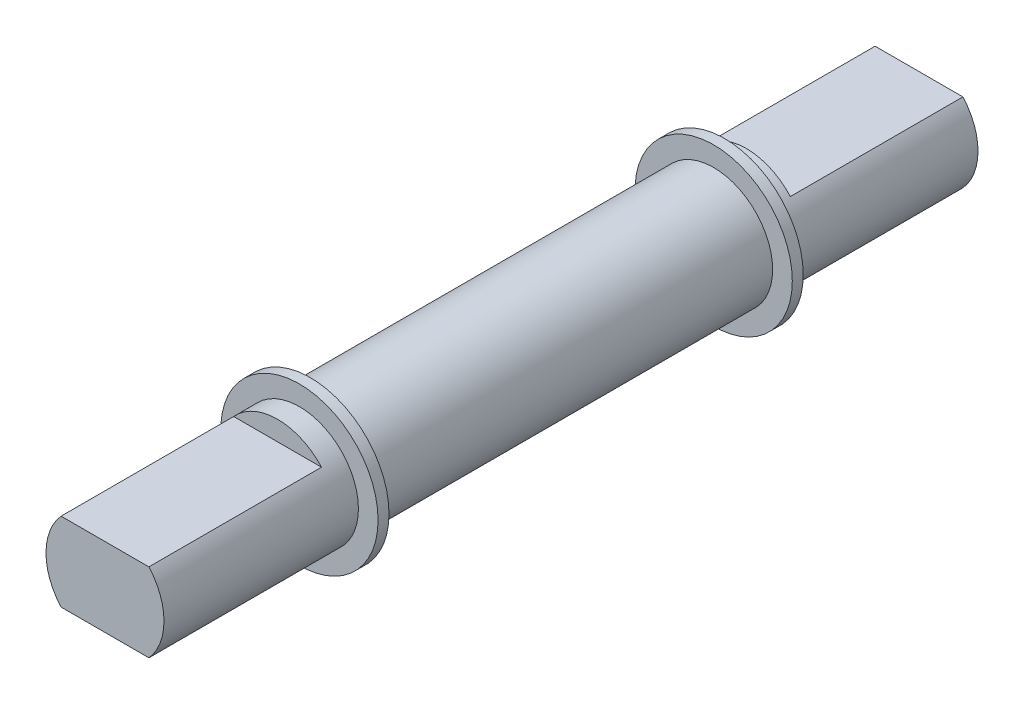
SolidWorks part; units mm, degrees
ref_plane "Front Plane" through (0, 0, 0) normal (0, 0, 1) x (1, 0, 0)
ref_plane "Top Plane" through (0, 0, 0) normal (0, 1, 0) x (1, 0, 0)
ref_plane "Right Plane" through (0, 0, 0) normal (1, 0, 0) x (0, 0, -1)
sketch "Sketch1" plane through (0, 0, 0) normal (0, 0, 1) x (1, 0, 0)
  circle A0 centre (0, 0) radius 2.7
  dimension "D1" = 5.4
extrude "Boss-Extrude1" add sketch "Sketch1" along normal mid plane 18.46
sketch "Sketch2" plane through (0, 0, 9.23) normal (0, 0, 1) x (1, 0, 0)
  circle A0 centre (0, 0) radius 3.6
  dimension "7.2" = 7.2
extrude "Boss-Extrude2" add sketch "Sketch2" along normal blind 0.5
sketch "Sketch3" plane through (0, 0, 9.73) normal (0, 0, 1) x (1, 0, 0)
  line L0 (-2.7, 0) -> (2.7, 0) construction
  line L1 (-2.01, 1.8027) -> (2.01, 1.8027)
  line L2 (-2.01, -1.8027) -> (2.01, -1.8027)
  circle A0 centre (0, 0) radius 2.7
  dimension "D1" = 5.4
  dimension "D2" = 4.02
  dimension "D3" = 4.02
extrude "Boss-Extrude3" add sketch "Sketch3" along normal blind 1 contours A0
extrude "Boss-Extrude4" add sketch "Sketch3<3>" along normal blind 8.9 contours A0 L0 L1 | L0 A0 L2 region at (0, 0.861, 9.73) region at (0, -0.861, 9.73)
sketch "Sketch3<3>" plane through (0, 0, 9.73) normal (0, 0, 1) x (1, 0, 0) same geometry as "Sketch3"
mirror "Mirror1" about plane through (0, 0, 0) normal (0, 0, 1) of "Boss-Extrude2", "Boss-Extrude3", "Boss-Extrude4"
